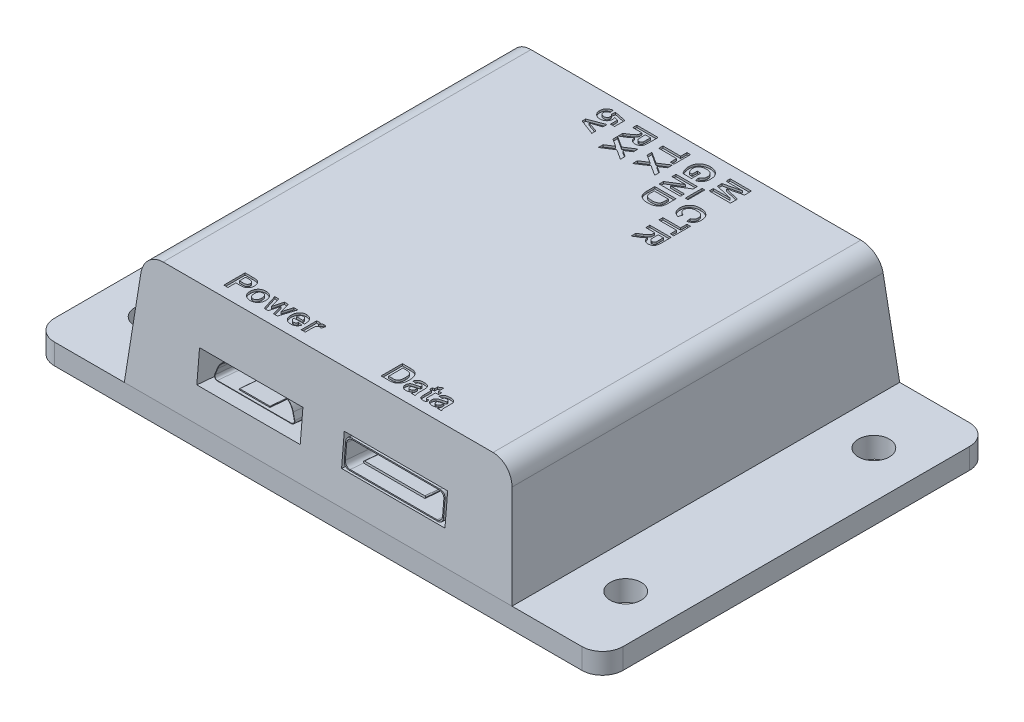
SolidWorks part; units mm, degrees
ref_plane "Front Plane" through (0, 0, 0) normal (0, 0, 1) x (1, 0, 0)
ref_plane "Top Plane" through (0, 0, 0) normal (0, 1, 0) x (1, 0, 0)
ref_plane "Right Plane" through (0, 0, 0) normal (1, 0, 0) x (0, 0, -1)
sketch "Sketch1" plane through (0, 0, 0) normal (0, 1, 0) x (1, 0, 0)
  line L1 (-18.75, 18.75) -> (18.75, 18.75)
  line L2 (-18.75, 18.75) -> (-18.75, -18.75)
  line L3 (-18.75, -18.75) -> (18.75, -18.75)
  line L4 (18.75, 18.75) -> (18.75, -18.75)
  point P4 (18.75, 0)
  point P5 (0, 18.75)
  dimension "D1" = 37.5
  dimension "D2" = 37.5
extrude "Boss-Extrude1" add sketch "Sketch1" along normal blind 11 draft 5
fillet "Fillet1" radius 2 2 edges at (-17.7876, 11, 0) (17.7876, 11, 0)
sketch "Sketch2" plane through (0, 0, 0) normal (0, -1, 0) x (1, 0, 0)
  line L0 (-18.75, 18.75) -> (18.75, 18.75) construction
  line L1 (-27.5, 18.75) -> (27.5, 18.75)
  line L2 (-27.5, 18.75) -> (-27.5, -18.75)
  line L3 (-27.5, -18.75) -> (27.5, -18.75)
  line L4 (27.5, 18.75) -> (27.5, -18.75)
  line L5 (18.75, -18.75) -> (-18.75, -18.75) construction
  point P9 (0, 18.75)
  dimension "D1" = 55
extrude "Boss-Extrude2" add sketch "Sketch2" along normal blind 2
fillet "Fillet2" radius 2 4 edges at (27.5, -1, -18.75) (27.5, -1, 18.75) (-27.5, -1, -18.75) (-27.5, -1, 18.75)
sketch "Sketch3" plane through (0, 1.628, 18.6076) normal (0, 0.0872, 0.9962) x (1, 0, 0)
  line L0 (-2, 2.9078) -> (2, 2.9078) construction
  line L1 (-12, 4.4078) -> (-2, 4.4078)
  line L2 (-12, 4.4078) -> (-12, 1.4078)
  line L3 (-12, 1.4078) -> (-2, 1.4078)
  line L4 (-2, 4.4078) -> (-2, 1.4078)
  line L5 (2, 4.4078) -> (12, 4.4078)
  line L6 (2, 4.4078) -> (2, 1.4078)
  line L7 (2, 1.4078) -> (12, 1.4078)
  line L8 (12, 4.4078) -> (12, 1.4078)
  line L9 (-15.955, 9.4078) -> (15.955, 9.4078) construction
  point P12 (0, 2.9078)
  dimension "D1" = 3
  dimension "D2" = 10
  dimension "D3" = 5
  dimension "D4" = 4
extrude "Cut-Extrude1" cut sketch "Sketch3" against normal blind 4
sketch "Sketch4" plane through (0, 1.628, -18.6076) normal (0, 0.0872, -0.9962) x (-1, 0, 0)
  line L0 (-15.955, 9.4078) -> (15.955, 9.4078) construction
  line L1 (-7.5, 5.4078) -> (7.5, 5.4078)
  line L2 (-7.5, 5.4078) -> (-7.5, -2.5922)
  line L3 (-7.5, -2.5922) -> (7.5, -2.5922)
  line L4 (7.5, 5.4078) -> (7.5, -2.5922)
  point P6 (0, 5.4078)
  dimension "D1" = 4
  dimension "D2" = 8
  dimension "D3" = 15
extrude "Cut-Extrude2" cut sketch "Sketch4" against normal blind 5
sketch "Sketch5" plane through (0, 1.2793, 14.6228) normal (0, 0.0872, 0.9962) x (1, 0, 0)
  line L0 (2, 4.4078) -> (2, 1.4078) construction
  line L2 (11.3, 1.6078) -> (2.7, 1.6078)
  line L3 (11.8, 2.1078) -> (11.8, 3.7078)
  line L4 (11.3, 4.2078) -> (2.7, 4.2078)
  line L5 (2.2, 2.1078) -> (2.2, 3.7078)
  line L6 (12, 4.4078) -> (2, 4.4078) construction
  line L8 (12, 1.4078) -> (12, 4.4078) construction
  line L9 (2, 1.4078) -> (12, 1.4078) construction
  line L10 (2.2, 2.9078) -> (11.8, 2.9078) construction
  line L11 (4.09, 3.0078) -> (9.91, 3.0078)
  line L12 (4, 2.9178) -> (4, 2.8978)
  line L13 (4.09, 2.8078) -> (9.91, 2.8078)
  line L14 (10, 2.9178) -> (10, 2.8978)
  line L15 (7, 4.2078) -> (7, 1.6078) construction
  line L17 (2.8, 4.1078) -> (11.2, 4.1078)
  line L18 (2.3, 3.6078) -> (2.3, 2.2078)
  line L19 (2.8, 1.7078) -> (11.2, 1.7078)
  line L20 (11.7, 3.6078) -> (11.7, 2.2078)
  arc A0 (11.3, 1.6078) -> (11.8, 2.1078) centre (11.3, 2.1078) ccw
  arc A1 (2.7, 1.6078) -> (2.2, 2.1078) centre (2.7, 2.1078) cw
  arc A2 (2.7, 4.2078) -> (2.2, 3.7078) centre (2.7, 3.7078) ccw
  arc A3 (11.8, 3.7078) -> (11.3, 4.2078) centre (11.3, 3.7078) ccw
  arc A4 (9.91, 2.8078) -> (10, 2.8978) centre (9.91, 2.8978) ccw
  arc A5 (9.91, 3.0078) -> (10, 2.9178) centre (9.91, 2.9178) cw
  arc A6 (4, 2.8978) -> (4.09, 2.8078) centre (4.09, 2.8978) ccw
  arc A7 (4.09, 3.0078) -> (4, 2.9178) centre (4.09, 2.9178) ccw
  arc A8 (11.2, 4.1078) -> (11.7, 3.6078) centre (11.2, 3.6078) cw
  arc A9 (11.2, 1.7078) -> (11.7, 2.2078) centre (11.2, 2.2078) ccw
  arc A10 (2.3, 2.2078) -> (2.8, 1.7078) centre (2.8, 2.2078) ccw
  arc A11 (2.8, 4.1078) -> (2.3, 3.6078) centre (2.8, 3.6078) ccw
  point P26 (4, 2.9078)
  point P29 (7, 3.0078)
  point P32 (10, 2.8078)
  point P35 (10, 3.0078)
  point P40 (4, 3.0078)
  dimension "D5" = 0.5
  dimension "D8" = 0.09
  dimension "D9" = 0.5
  dimension "D1" = 0.2
  dimension "D2" = 0.2
  dimension "D3" = 0.2
  dimension "D4" = 0.2
  dimension "D6" = 6
  dimension "D7" = 0.2
  dimension "D10" = 0.1
  dimension "D11" = 0.1
  dimension "D12" = 0.1
  dimension "D13" = 0.1
extrude "Boss-Extrude3" add sketch "Sketch5" along normal blind 4 contours L3 A3 L4 A2 L5 A1 L2 A0 A11 L17 A8 L20 A9 L19 A10 L18 | L13 A4 L14 A5 L11 A7 L12 A6 region at (7, 2.9801, 14.474)
sketch "Sketch6" plane through (0, 1.2793, 14.6228) normal (0, 0.0872, 0.9962) x (1, 0, 0)
  line L0 (-2, 4.4078) -> (-12, 4.4078) construction
  line L1 (-9.25, 4.2078) -> (-4.75, 4.2078)
  line L2 (-10.6721, 3.1851) -> (-10.8673, 2.6033)
  line L3 (-10.5829, 2.2078) -> (-3.4171, 2.2078)
  line L4 (-3.3279, 3.1851) -> (-3.1327, 2.6033)
  line L5 (-7, 1.4078) -> (-7, 4.4078) construction
  line L6 (-12, 1.4078) -> (-2, 1.4078) construction
  line L8 (-8.46, 2.6033) -> (-5.54, 2.6033)
  line L9 (-8.5, 2.5633) -> (-8.5, 2.5433)
  line L10 (-8.46, 2.5033) -> (-5.54, 2.5033)
  line L11 (-5.5, 2.5633) -> (-5.5, 2.5433)
  arc A4 (-4.75, 4.2078) -> (-3.3279, 3.1851) centre (-4.75, 2.7078) cw
  arc A5 (-9.25, 4.2078) -> (-10.6721, 3.1851) centre (-9.25, 2.7078) ccw
  arc A6 (-3.4171, 2.2078) -> (-3.1327, 2.6033) centre (-3.4171, 2.5078) ccw
  arc A7 (-10.8673, 2.6033) -> (-10.5829, 2.2078) centre (-10.5829, 2.5078) ccw
  arc A8 (-5.54, 2.5033) -> (-5.5, 2.5433) centre (-5.54, 2.5433) ccw
  arc A9 (-5.54, 2.6033) -> (-5.5, 2.5633) centre (-5.54, 2.5633) cw
  arc A10 (-8.5, 2.5433) -> (-8.46, 2.5033) centre (-8.46, 2.5433) ccw
  arc A11 (-8.46, 2.6033) -> (-8.5, 2.5633) centre (-8.46, 2.5633) ccw
  point P4 (-7, 4.2078)
  point P7 (-7, 2.6033)
  point P14 (-7, 2.2078)
  point P23 (-5.5, 2.6033)
  point P28 (-3, 2.2078)
  point P31 (-11, 2.2078)
  point P33 (-8.5, 2.5033)
  point P37 (-8.5, 2.6033)
  dimension "D1" = 1.5
  dimension "D2" = 0.3
  dimension "D10" = 0.04
  dimension "D3" = 2
  dimension "D4" = 0.2
  dimension "D5" = 8
  dimension "D6" = 4.5
  dimension "D7" = 7.7346
  dimension "D8" = 0.1
  dimension "D9" = 3
extrude "Extrude-Thin2" add sketch "Sketch6" along normal blind 3.5 thin thin type one direction reverse wall 0.04
sketch "Sketch8" plane through (0, 1.5844, 18.1095) normal (0, 0.0872, 0.9962) x (1, 0, 0)
  line L0 (-5.54, 2.5633) -> (-8.46, 2.5633) construction
  line L1 (-5.54, 2.5633) -> (-8.46, 2.5633)
  line L2 (-8.46, 2.5433) -> (-5.54, 2.5433) construction
  line L3 (-8.46, 2.5433) -> (-5.54, 2.5433)
  line L4 (-8.46, 2.5633) -> (-8.46, 2.5433) construction
  line L5 (-8.46, 2.5633) -> (-8.46, 2.5433)
  line L6 (-5.54, 2.5433) -> (-5.54, 2.5633) construction
  line L7 (-5.54, 2.5433) -> (-5.54, 2.5633)
extrude "Boss-Extrude5" add sketch "Sketch8" against normal blind 3.5
sketch "Sketch9" plane through (0, 11, 0) normal (0, 1, 0) x (1, 0, 0)
  line L0 (-12, -16.7876) -> (-2, -16.7876) construction
  line L1 (0, 0) -> (0, -17.7876) construction
  line L2 (-15.955, -17.7876) -> (15.955, -17.7876) construction
  line L3 (12, -16.7876) -> (2, -16.7876) construction
  line L4 (-7.5, 16.7876) -> (7.5, 16.7876) construction
  line L5 (15.955, 17.7876) -> (-15.955, 17.7876) construction
  line L6 (-7.5, 16.7876) -> (-7.5, 7.7876) construction
  line L7 (-4.5, 16.7876) -> (-4.5, 7.7876) construction
  line L8 (-1.5, 16.7876) -> (-1.5, 7.7876) construction
  line L9 (1.5, 16.7876) -> (1.5, 7.7876) construction
  line L10 (4.5, 16.7876) -> (4.5, 7.7876) construction
  text T0 "Power" font "Arial" height in points 8
  text T1 "Data" font "Arial" height in points 8
  text T2 "5v" font "Arial" height in points 8
  text T3 "RX" font "Arial" height in points 8
  text T4 "TX" font "Arial" height in points 8
  text T5 "GND" font "Arial" height in points 8
  text T6 "M_CTR" font "Arial" height in points 8
  point P8 (0, 16.7876)
  dimension "D1" = 2
  dimension "D2" = 10
  dimension "D3" = 1
  dimension "D4" = 15
  dimension "D5" = 1
  dimension "D6" = 9
  dimension "D8" = 3
  dimension "D7" = 5
extrude "Cut-Extrude3" cut sketch "Sketch9" against normal blind 0.2
sketch "Sketch10" plane through (0, 0, 0) normal (0, 1, 0) x (1, 0, 0)
  line L0 (-27.5, 0) -> (27.5, 0) construction
  line L1 (0, 17.7876) -> (0, -17.7876) construction
  line L2 (15.955, 17.7876) -> (-15.955, 17.7876) construction
  line L3 (-15.955, -17.7876) -> (15.955, -17.7876) construction
  line L4 (-27.5, -16.75) -> (-27.5, 16.75) construction
  line L5 (27.5, 16.75) -> (27.5, -16.75) construction
  line L6 (-25.5, 18.75) -> (-18.75, 18.75) construction
  circle A0 centre (-23, 12) radius 1.5
  circle A1 centre (-23, -12) radius 1.5
  circle A2 centre (23, -12) radius 1.5
  circle A3 centre (23, 12) radius 1.5
  dimension "D1" = 3
  dimension "D2" = 51.8845
  dimension "D3" = 24
  dimension "D4" = 6.75
  dimension "D5" = 46
extrude "Cut-Extrude4" cut sketch "Sketch10" against normal through all
sketch "Sketch11" plane through (0, 1.1922, -13.6266) normal (0, 0.0872, -0.9962) x (-1, 0, 0)
  line L0 (-7.5, -2.5922) -> (7.5, -2.5922) construction
  line L1 (-5.75, 2.9078) -> (5.75, 2.9078)
  line L2 (-5.75, 2.9078) -> (-5.75, -1.0922)
  line L3 (-5.75, -1.0922) -> (5.75, -1.0922)
  line L4 (5.75, 2.9078) -> (5.75, -1.0922)
  line L5 (-4.15, 2.1578) -> (-4.15, -0.3422) construction
  line L6 (-2.75, -1.0922) -> (2.75, -1.0922)
  line L7 (-2.75, -1.0922) -> (-2.75, -1.3922)
  line L8 (-2.75, -1.3922) -> (2.75, -1.3922)
  line L9 (2.75, -1.0922) -> (2.75, -1.3922)
  line L10 (-4.75, 1.8578) -> (-3.55, 1.8578)
  line L11 (-4.75, 1.8578) -> (-4.75, -0.3422)
  line L12 (-4.75, -0.3422) -> (-3.55, -0.3422)
  line L13 (-3.55, 1.8578) -> (-3.55, -0.3422)
  line L14 (-4.45, 2.1578) -> (-3.85, 2.1578)
  line L15 (-4.45, 2.1578) -> (-4.45, 1.8578)
  line L16 (-4.45, 1.8578) -> (-3.85, 1.8578)
  line L17 (-3.85, 2.1578) -> (-3.85, 1.8578)
  line L18 (-5.75, 0.9078) -> (5.75, 0.9078) construction
  line L19 (-2.675, 1.8578) -> (-2.675, -0.3422)
  line L20 (-2.675, 1.8578) -> (-1.475, 1.8578)
  line L21 (-1.475, 1.8578) -> (-1.475, -0.3422)
  line L22 (-2.675, -0.3422) -> (-1.475, -0.3422)
  line L23 (-2.375, 2.1578) -> (-2.375, 1.8578)
  line L24 (-2.375, 2.1578) -> (-1.775, 2.1578)
  line L25 (-1.775, 2.1578) -> (-1.775, 1.8578)
  line L26 (-2.375, 1.8578) -> (-1.775, 1.8578)
  line L27 (-0.6, 1.8578) -> (-0.6, -0.3422)
  line L28 (-0.6, 1.8578) -> (0.6, 1.8578)
  line L29 (0.6, 1.8578) -> (0.6, -0.3422)
  line L30 (-0.6, -0.3422) -> (0.6, -0.3422)
  line L31 (-0.3, 2.1578) -> (-0.3, 1.8578)
  line L32 (-0.3, 2.1578) -> (0.3, 2.1578)
  line L33 (0.3, 2.1578) -> (0.3, 1.8578)
  line L34 (-0.3, 1.8578) -> (0.3, 1.8578)
  line L35 (1.475, 1.8578) -> (1.475, -0.3422)
  line L36 (1.475, 1.8578) -> (2.675, 1.8578)
  line L37 (2.675, 1.8578) -> (2.675, -0.3422)
  line L38 (1.475, -0.3422) -> (2.675, -0.3422)
  line L39 (1.775, 2.1578) -> (1.775, 1.8578)
  line L40 (1.775, 2.1578) -> (2.375, 2.1578)
  line L41 (2.375, 2.1578) -> (2.375, 1.8578)
  line L42 (1.775, 1.8578) -> (2.375, 1.8578)
  line L43 (3.55, 1.8578) -> (3.55, -0.3422)
  line L44 (3.55, 1.8578) -> (4.75, 1.8578)
  line L45 (4.75, 1.8578) -> (4.75, -0.3422)
  line L46 (3.55, -0.3422) -> (4.75, -0.3422)
  line L47 (3.85, 2.1578) -> (3.85, 1.8578)
  line L48 (3.85, 2.1578) -> (4.45, 2.1578)
  line L49 (4.45, 2.1578) -> (4.45, 1.8578)
  line L50 (3.85, 1.8578) -> (4.45, 1.8578)
  point P4 (0, 2.9078)
  point P12 (0, -1.3922)
  point P23 (-4.15, 0.9078)
  point P24 (-4.15, 2.1578)
  dimension "D1" = 4
  dimension "D2" = 11.5
  dimension "D3" = 1.5
  dimension "D4" = 5.5
  dimension "D5" = 0.3
  dimension "D6" = 1.2
  dimension "D7" = 0.6
  dimension "D8" = 1
  dimension "D9" = 2.5
  dimension "D10" = 0.3
  dimension "D12" = 1
  dimension "D11" = 5
extrude "Boss-Extrude6" add sketch "Sketch11" along normal blind 5 contours L4 L1 L2 L3 L14 L17 L10 L13 L12 L11 L15 L24 L25 L20 L21 L22 L19 L23 L32 L33 L28 L29 L30 L27 L31 L40 L41 L36 L37 L38 L35 L39 L48 L49 L44 L45 L46 L43 L47 region at (0, 3.9677, -13.3838)
